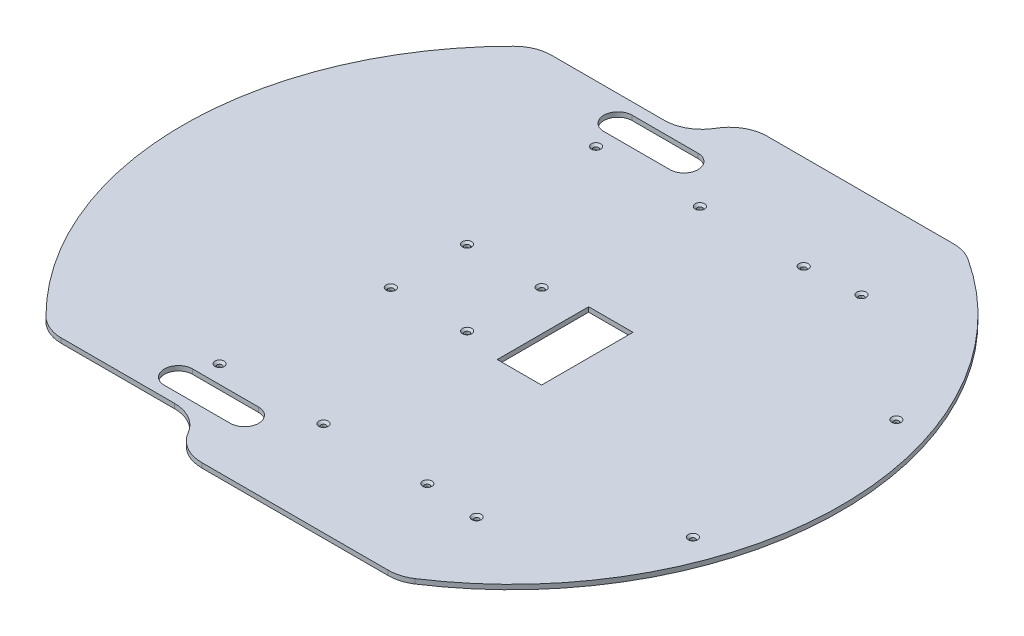
SolidWorks part; units mm, degrees
ref_plane "Plan de face" through (0, 0, 0) normal (0, 0, 1) x (1, 0, 0)
ref_plane "Plan de dessus" through (0, 0, 0) normal (0, 1, 0) x (1, 0, 0)
ref_plane "Plan de droite" through (0, 0, 0) normal (1, 0, 0) x (0, 0, -1)
sketch "Esquisse1" plane through (0, 0, 0) normal (0, 1, 0) x (1, 0, 0)
  line L0 (-138.94, 165.455) -> (-62.65, 165.455)
  line L5 (106.95, -190.145) -> (-18.65, -190.145)
  line L7 (-18.65, 190.855) -> (106.95, 190.855)
  line L8 (-138.94, -164.745) -> (-62.65, -164.745)
  arc A1 (-156.83, 157.725) -> (-138.94, 165.455) centre (-138.5811, 140.0575) cw
  arc A2 (-62.65, 165.455) -> (-40.65, 178.155) centre (-62.647, 190.855) ccw
  arc A3 (-40.65, 178.155) -> (-18.65, 190.855) centre (-18.653, 165.455) cw
  arc A4 (106.95, 190.855) -> (120.78, 186.755) centre (106.9427, 165.455) cw
  arc A5 (120.78, 186.755) -> (120.78, -186.045) centre (-0.716, 0.355) cw
  arc A6 (120.78, -186.045) -> (106.95, -190.145) centre (106.9427, -164.745) cw
  arc A7 (-18.65, -190.145) -> (-40.65, -177.445) centre (-18.653, -164.745) cw
  arc A8 (-40.65, -177.445) -> (-62.65, -164.745) centre (-62.647, -190.145) ccw
  arc A9 (-156.83, -157.015) -> (-138.94, -164.745) centre (-138.5811, -139.3475) ccw
  arc A10 (-156.83, 157.725) -> (-156.83, -157.015) centre (0.4625, 0.355) ccw
  point P0 (0, 0)
  dimension "D3" = 222.5
  dimension "D5" = 25.4
  dimension "D7" = 25.4
  dimension "D9" = 25.4
  dimension "D12" = 25.4
  dimension "D14" = 222.5
  dimension "D15" = 25.4
  dimension "D18" = 25.4
  dimension "D19" = 76.29
  dimension "D21" = 25.4
  dimension "D22" = 25.4
  dimension "D2" = 125.6
  dimension "D4" = 157.725
  dimension "D6" = 76.29
  dimension "D8" = 22
  dimension "D10" = 22
  dimension "D11" = 125.6
  dimension "D13" = 4.1
  dimension "D16" = 4.1
  dimension "D17" = 13.83
  dimension "D20" = 22
  dimension "D23" = 381
  dimension "D24" = 277.61
  dimension "D25" = 330.2
  dimension "D26" = 22
  dimension "D27" = 17.89
  dimension "D28" = 17.89
  dimension "D29" = 7.73
  dimension "D30" = 7.73
  dimension "D31" = 25.4
  dimension "D32" = 156.83
extrude "Boss.-Extru.1" add sketch "Esquisse1" along normal blind 3.18
sketch "Esquisse2" plane through (0, 3.18, 0) normal (0, 1, 0) x (1, 0, 0)
  line L0 (-76.45, -148.105) -> (-32, -148.105) construction
  line L1 (-76.45, -138.575) -> (-32, -138.575)
  line L2 (-76.45, -157.635) -> (-32, -157.635)
  line L3 (-138.94, -164.745) -> (-62.65, -164.745) construction
  line L4 (0, 0) -> (-294.8551, 0) construction
  line L5 (-76.45, 148.105) -> (-32, 148.105) construction
  line L6 (-76.45, 138.575) -> (-32, 138.575)
  line L7 (-76.45, 157.635) -> (-32, 157.635)
  line L8 (20.7, -30.425) -> (50.55, -30.425)
  line L9 (20.7, -30.425) -> (20.7, 31.175)
  line L10 (20.7, 31.175) -> (50.55, 31.175)
  line L11 (50.55, -30.425) -> (50.55, 31.175)
  arc A0 (-76.45, -138.575) -> (-76.45, -157.635) centre (-76.45, -148.105) ccw
  arc A1 (-32, -157.635) -> (-32, -138.575) centre (-32, -148.105) ccw
  arc A2 (-76.45, 138.575) -> (-76.45, 157.635) centre (-76.45, 148.105) cw
  arc A3 (-32, 157.635) -> (-32, 138.575) centre (-32, 148.105) cw
  point P2 (-54.225, -148.105)
  point P15 (-54.225, 148.105)
  dimension "D1" = 9.53
  dimension "D2" = 7.11
  dimension "D3" = 13.8
  dimension "D4" = 44.45
  dimension "D5" = 61.6
  dimension "D6" = 159.64
  dimension "D7" = 134.32
  dimension "D8" = 29.85
extrude "Enlèv. mat.-Extru.1" cut sketch "Esquisse2" against normal blind 3.18
sketch "Esquisse3" plane through (0, 3.18, 0) normal (0, 1, 0) x (1, 0, 0)
  line L1 (0.4625, 0.355) -> (-274.8168, 0.355) construction
  point P0 (-70.35, -126.475)
  point P1 (-0.37, -126.475)
  point P3 (69.61, -126.475)
  point P5 (105.7, -129.345)
  point P8 (190.32, -68.205)
  point P10 (190.32, 68.915)
  point P11 (105.7, 130.055)
  point P12 (69.61, 127.185)
  point P13 (-0.37, 127.185)
  point P14 (-70.35, 127.185)
  dimension "D1" = 12.1
  dimension "D2" = 6.1
  dimension "D3" = 69.98
  dimension "D4" = 69.98
  dimension "D5" = 2.87
  dimension "D6" = 36.09
  dimension "D7" = 84.62
  dimension "D8" = 61.14
hole_wizard "Fraisage pour vis à tête fraisée M31" positions "Esquisse3D2" profile "Esquisse8" countersink size "M3" standard "Ansi Metric" end condition through all
sketch3d "Esquisse3D2"
  point P0 (-70.35, 3.18, 126.475)
  point P3 (-0.37, 3.18, 126.475)
  point P6 (69.61, 3.18, 126.475)
  point P9 (105.7, 3.18, 129.345)
  point P12 (190.32, 3.18, 68.205)
  point P15 (190.32, 3.18, -68.915)
  point P18 (105.7, 3.18, -130.055)
  point P21 (69.61, 3.18, -127.185)
  point P24 (-0.37, 3.18, -127.185)
  point P27 (-70.35, 3.18, -127.185)
sketch "Esquisse8" plane through (-70.35, 3.18, 126.475) normal (1, 0, 0) x (0, 0, 1)
  line L0 (0, 0) -> (0, 3.18)
  line L1 (0, 3.18) -> (1.7, 3.18)
  line L2 (1.7, 3.18) -> (1.7, 1.45)
  line L3 (1.7, 1.45) -> (3.15, 0)
  line L5 (3.15, 0) -> (0, 0)
  line L6 (-1.7, 1.45) -> (-3.15, 0) construction
  line L11 (0, -6.35) -> (0, 107.95) construction
  dimension "Diamètre du perçage jusqu'au prochain" = 3.4
  dimension "Profondeur du perçage jusqu'au prochain" = 3.18
  dimension "Diamètre du fraisage entrant" = 6.3
  dimension "Angle du fraisage entrant" = 90
sketch "Esquisse9" plane through (0, 3.18, 0) normal (0, 1, 0) x (1, 0, 0)
  line L0 (20.7, 31.175) -> (20.7, -30.425) construction
  line L1 (-129.4413, 0.355) -> (65.4144, -112.145) construction
  line L2 (65.4144, -112.145) -> (65.4144, 112.855) construction
  line L3 (65.4144, 112.855) -> (-129.4413, 0.355) construction
  line L13 (-4.72, 27.445) -> (-4.72, -26.555) construction
  line L14 (-4.72, -26.555) -> (-59.23, -26.5244) construction
  line L15 (-59.23, -26.5244) -> (-58.3786, 27.829) construction
  line L16 (-58.3786, 27.829) -> (-4.72, 27.445) construction
  circle A0 centre (0.4625, 0.355) radius 64.9519 construction
  dimension "D2" = 54.36
  dimension "D1" = 225
  dimension "D3" = 54
  dimension "D4" = 3.73
  dimension "D5" = 25.42
  dimension "D6" = 53.66
  dimension "D7" = 54.51
  dimension "D8" = 90.41
  dimension "D9" = 90.487
sketch "Esquisse11" plane through (0, 3.18, 0) normal (0, 1, 0) x (1, 0, 0)
  line L0 (-56.7023, 26.6179) -> (-6.06, -23.9834) construction
  line L1 (-58.3929, 28.3229) -> (-4.7329, 28.3229) construction
  line L2 (-58.3929, 28.3229) -> (-58.8527, -26.0352) construction
  line L3 (-58.8527, -26.0352) -> (-4.3427, -25.6771) construction
  line L4 (-4.7329, 28.3229) -> (-4.3427, -25.6771) construction
  circle A0 centre (-56.7023, 26.6179) radius 1.705 construction
  circle A1 centre (-6.06, -23.9834) radius 1.705 construction
  circle A2 centre (-57.1331, -24.3188) radius 1.705 construction
  circle A3 centre (-6.4256, 26.6179) radius 1.705 construction
  point P6 (-4.5378, 1.3229)
  dimension "D5" = 3.41
  dimension "D6" = 54.51
  dimension "D1" = 54.36
  dimension "D2" = 71.59
  dimension "D3" = 53.66
  dimension "D4" = 54
  dimension "D7" = 26
  dimension "D8" = 4.5378
hole_wizard "Fraisage pour vis à tête fraisée M33" positions "Esquisse3D4" profile "Esquisse12" countersink size "M3" standard "Ansi Metric" end condition through all
sketch3d "Esquisse3D4"
  point P0 (-56.7023, 3.18, -26.6179)
  point P3 (-6.4256, 3.18, -26.6179)
  point P6 (-6.06, 3.18, 23.9834)
  point P9 (-57.1331, 3.18, 24.3188)
sketch "Esquisse12" plane through (-56.7023, 3.18, -26.6179) normal (1, 0, 0) x (0, 0, 1)
  line L0 (0, 0) -> (0, 3.18)
  line L1 (0, 3.18) -> (1.8, 3.18)
  line L2 (1.8, 3.18) -> (1.8, 1.35)
  line L3 (1.8, 1.35) -> (3.15, 0)
  line L5 (3.15, 0) -> (0, 0)
  line L6 (-1.8, 1.35) -> (-3.15, 0) construction
  line L11 (0, -6.35) -> (0, 107.95) construction
  dimension "Diamètre du perçage jusqu'au prochain" = 3.6
  dimension "Profondeur du perçage jusqu'au prochain" = 3.18
  dimension "Diamètre du fraisage entrant" = 6.3
  dimension "Angle du fraisage entrant" = 90
sketch "Esquisse13" plane through (0, 3.18, 3.18) normal (0, 1, 0) x (1, 0, 0)
  line L24 (-106.3, -60.5905) -> (3.7, -60.5905) construction
  line L29 (-106.3, -60.5905) -> (-106.3, 49.4095) construction
  line L30 (-106.3, 49.4095) -> (3.7, 49.4095) construction
  line L31 (3.7, 49.4095) -> (3.7, -60.5905) construction
  line L70 (58.8962, -113.6751) -> (84.877, -98.6751) construction
  line L71 (-130.2613, 25.535) -> (-128.6213, 25.535) construction
  line L72 (-130.2613, 25.535) -> (-130.2613, -4.465) construction
  line L73 (-130.2613, -4.465) -> (-128.6213, -4.465) construction
  line L74 (-128.6213, 25.535) -> (-128.6213, -4.465) construction
  line L75 (65.4144, -108.965) -> (65.4144, 116.035) construction
  line L76 (65.4144, 116.035) -> (-129.4413, 3.535) construction
  line L77 (-129.4413, 3.535) -> (65.4144, -108.965) construction
  line L82 (84.877, -98.6751) -> (84.057, -97.2549) construction
  line L83 (84.057, -97.2549) -> (58.0762, -112.2549) construction
  line L84 (58.0762, -112.2549) -> (58.8962, -113.6751) construction
  line L85 (58.0762, 119.3249) -> (84.057, 104.3249) construction
  line L86 (84.057, 104.3249) -> (84.877, 105.7451) construction
  line L87 (84.877, 105.7451) -> (58.8962, 120.7451) construction
  line L88 (58.8962, 120.7451) -> (58.0762, 119.3249) construction
  line L89 (65.4144, -108.965) -> (65.4144, 116.035) construction
  line L90 (65.4144, 116.035) -> (-129.4413, 3.535) construction
  circle A4 centre (-129.4413, 3.535) radius 5 construction
  circle A5 centre (65.4144, 116.035) radius 5 construction
  circle A6 centre (65.4144, -108.965) radius 5 construction
  circle A7 centre (69.6144, -123.295) radius 3.15 construction
  circle A8 centre (105.7044, -126.165) radius 3.15 construction
  circle A9 centre (69.6144, 130.365) radius 3.15 construction
  circle A10 centre (105.7044, 133.235) radius 3.15 construction
  circle A11 centre (0.4625, 3.535) radius 64.9519 construction
  dimension "D9" = 4.2
  dimension "D12" = 14.33
  dimension "D13" = 4.2
  dimension "D14" = 36.09
  dimension "D27" = 8
  dimension "D31" = 1.64
  dimension "D32" = 0.82
  dimension "D33" = 8
  dimension "D34" = 225
  dimension "D2" = 106.7625
  dimension "D3" = 60
  dimension "D4" = 60
  dimension "D5" = 60
  dimension "D6" = 110
  dimension "D7" = 110
  dimension "D8" = 14.33
  dimension "D10" = 36.09
  dimension "D11" = 2.87
  dimension "D15" = 2.87
  dimension "D16" = 0
  dimension "D17" = 0
  dimension "D18" = 0
  dimension "D19" = 0
  dimension "D20" = 1.64
  dimension "D21" = 8
  dimension "D22" = 0.82
  dimension "D23" = 1.64
  dimension "D24" = 30
  dimension "D25" = 30
  dimension "D28" = 0.82
  dimension "D29" = 60
  dimension "D30" = 30
  dimension "D35" = 60
